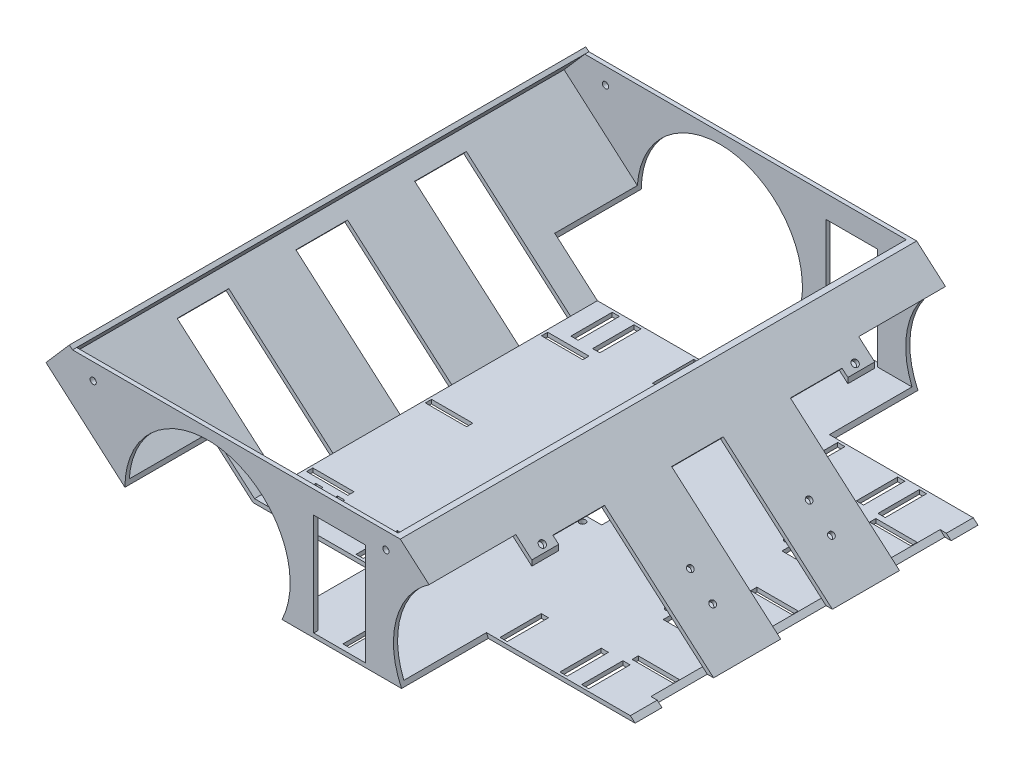
SolidWorks part; units mm, degrees
material "AISI 304"
ref_plane "前视基准面" through (0, 0, 0) normal (0, 0, 1) x (1, 0, 0)
ref_plane "上视基准面" through (0, 0, 0) normal (0, 1, 0) x (1, 0, 0)
ref_plane "右视基准面" through (0, 0, 0) normal (1, 0, 0) x (0, 0, -1)
sketch "草图1" plane through (0, 0, 0) normal (0, 0, 1) x (1, 0, 0)
  line L0 (0, 0) -> (-185, 0)
  line L1 (-185, 0) -> (-256.6974, 62.3256)
  line L2 (-256.6974, 62.3256) -> (-71.6974, 62.3256)
  line L3 (-71.6974, 62.3256) -> (0, 0)
extrude "凸台-拉伸1" add sketch "草图1" along normal blind 250
shell "抽壳1" thickness 2 removed face at (-164.1974, 62.3256, 125)
sketch "草图4" plane through (0, 0, 250) normal (0, 0, 1) x (1, 0, 0)
  circle A0 centre (-35, 17.3) radius 40
  circle A1 centre (-165, 17.3) radius 40
extrude "切除-拉伸3" cut sketch "草图4" against normal blind 42
sketch "草图6" plane through (0, 0, 0) normal (0, 0, -1) x (-1, 0, 0)
  arc A0 (15.1851, -17.4472) -> (15.1851, 52.0472) centre (35, 17.3) ccw
  arc A1 (15.1851, 52.0472) -> (15.1851, -17.4472) centre (-5, 17.3) ccw
  circle A2 centre (165, 17.3) radius 40
extrude "切除-拉伸5" cut sketch "草图6" against normal blind 42 contours A2 | A0 A1
sketch "草图7" plane through (0, 2, 0) normal (0, 1, 0) x (1, 0, 0)
  line L0 (-184.2522, -125) -> (127.4873, -125) construction
  line L1 (-184.2522, -208) -> (-184.2522, -42) construction
  line L2 (-175.84, -206.75) -> (-172.34, -206.75)
  line L7 (-175.84, -206.75) -> (-175.84, -186.75)
  line L8 (-175.84, -186.75) -> (-172.34, -186.75)
  line L9 (-172.34, -206.75) -> (-172.34, -186.75)
  line L10 (-27.16, -206.75) -> (-23.66, -206.75)
  line L11 (-27.16, -206.75) -> (-27.16, -186.75)
  line L12 (-27.16, -186.75) -> (-23.66, -186.75)
  line L13 (-23.66, -206.75) -> (-23.66, -186.75)
  line L14 (-165.34, -206.75) -> (-161.84, -206.75)
  line L15 (-165.34, -206.75) -> (-165.34, -186.75)
  line L16 (-165.34, -186.75) -> (-161.84, -186.75)
  line L17 (-161.84, -206.75) -> (-161.84, -186.75)
  line L18 (-136.34, -206.75) -> (-132.84, -206.75)
  line L19 (-136.34, -206.75) -> (-136.34, -186.75)
  line L20 (-136.34, -186.75) -> (-132.84, -186.75)
  line L21 (-132.84, -206.75) -> (-132.84, -186.75)
  line L22 (-34.16, -206.75) -> (-37.66, -206.75)
  line L23 (-34.16, -206.75) -> (-34.16, -186.75)
  line L24 (-34.16, -186.75) -> (-37.66, -186.75)
  line L25 (-37.66, -206.75) -> (-37.66, -186.75)
  line L26 (-63.16, -206.75) -> (-66.66, -206.75)
  line L27 (-63.16, -206.75) -> (-63.16, -186.75)
  line L28 (-63.16, -186.75) -> (-66.66, -186.75)
  line L29 (-66.66, -206.75) -> (-66.66, -186.75)
  line L30 (-132.84, -43.25) -> (-132.84, -63.25)
  line L31 (-136.34, -63.25) -> (-132.84, -63.25)
  line L32 (-136.34, -43.25) -> (-136.34, -63.25)
  line L33 (-136.34, -43.25) -> (-132.84, -43.25)
  line L34 (-161.84, -43.25) -> (-161.84, -63.25)
  line L35 (-165.34, -63.25) -> (-161.84, -63.25)
  line L36 (-165.34, -43.25) -> (-165.34, -63.25)
  line L37 (-165.34, -43.25) -> (-161.84, -43.25)
  line L38 (-172.34, -43.25) -> (-172.34, -63.25)
  line L39 (-175.84, -63.25) -> (-172.34, -63.25)
  line L40 (-175.84, -43.25) -> (-175.84, -63.25)
  line L41 (-175.84, -43.25) -> (-172.34, -43.25)
  line L42 (-66.66, -43.25) -> (-66.66, -63.25)
  line L43 (-63.16, -63.25) -> (-66.66, -63.25)
  line L44 (-63.16, -43.25) -> (-63.16, -63.25)
  line L45 (-63.16, -43.25) -> (-66.66, -43.25)
  line L46 (-37.66, -43.25) -> (-37.66, -63.25)
  line L47 (-34.16, -63.25) -> (-37.66, -63.25)
  line L48 (-34.16, -43.25) -> (-34.16, -63.25)
  line L49 (-34.16, -43.25) -> (-37.66, -43.25)
  line L50 (-23.66, -43.25) -> (-23.66, -63.25)
  line L51 (-27.16, -63.25) -> (-23.66, -63.25)
  line L52 (-27.16, -43.25) -> (-27.16, -63.25)
  line L53 (-27.16, -43.25) -> (-23.66, -43.25)
  line L54 (-24.66, -90.25) -> (-24.66, -105.5276) construction
  line L55 (-101.1743, -135) -> (-89.1743, -135)
  line L56 (-101.1743, -135) -> (-101.1743, -115)
  line L57 (-101.1743, -115) -> (-89.1743, -115)
  line L58 (-89.1743, -135) -> (-89.1743, -115)
  line L59 (-101.1743, -135) -> (-89.1743, -115) construction
  line L60 (-101.1743, -115) -> (-89.1743, -135) construction
  line L61 (-34.66, -90.25) -> (-14.66, -90.25)
  line L62 (-34.66, -90.25) -> (-34.66, -102.25)
  line L63 (-34.66, -102.25) -> (-14.66, -102.25)
  line L64 (-14.66, -90.25) -> (-14.66, -102.25)
  line L65 (-14.66, -159.75) -> (-14.66, -147.75)
  line L66 (-34.66, -147.75) -> (-14.66, -147.75)
  line L67 (-34.66, -159.75) -> (-34.66, -147.75)
  line L68 (-34.66, -159.75) -> (-14.66, -159.75)
  circle A0 centre (-95.1743, -111.75) radius 1.5
  circle A1 centre (-95.1743, -138.25) radius 1.5
  circle A2 centre (-11.41, -96.25) radius 1.5
  circle A3 centre (-37.91, -96.25) radius 1.5
  circle A4 centre (-37.91, -153.75) radius 1.5
  circle A5 centre (-11.41, -153.75) radius 1.5
  point P52 (-95.1743, -125)
  dimension "D2" = 29
  dimension "D3" = 26.5
  dimension "D6" = 3
  dimension "D1" = 10.5
  dimension "D4" = 26.5
  dimension "D5" = 20
  dimension "D7" = 81.75
  dimension "D8" = 81.75
  dimension "D9" = 81.75
  dimension "D10" = 81.75
extrude "切除-拉伸6" cut sketch "草图7" against normal blind 32
sketch "草图8" plane through (0, 0, 208) normal (0, 0, 1) x (1, 0, 0)
  line L1 (-50, 52) -> (0, 52)
  line L2 (-50, 52) -> (-50, 2)
  line L3 (-50, 2) -> (0, 2)
  line L4 (0, 52) -> (0, 2)
extrude "切除-拉伸7" cut sketch "草图8" against normal blind 15
sketch "草图9" plane through (0, 0, 42) normal (0, 0, -1) x (-1, 0, 0)
  line L0 (50, 2) -> (0, 2)
  line L2 (0, 2) -> (0, 50)
  line L3 (0, 50) -> (50, 50)
  line L4 (50, 2) -> (50, 50)
  line L5 (5.3492, 2) -> (71.9582, 2) construction
extrude "切除-拉伸8" cut sketch "草图9" against normal blind 15
sketch "草图10" plane through (0, 0, 0) normal (0.6561, 0.7547, 0) x (0.7547, -0.6561, 0)
  line L0 (0, -208) -> (0, -42) construction
  line L1 (0, -170) -> (-70, -170)
  line L2 (0, -170) -> (0, -195)
  line L3 (0, -195) -> (-70, -195)
  line L4 (-70, -170) -> (-70, -195)
  line L6 (0, -55) -> (-70, -55)
  line L7 (0, -55) -> (0, -80)
  line L8 (0, -80) -> (-70, -80)
  line L9 (-70, -55) -> (-70, -80)
  line L10 (0, -112.5) -> (-70, -112.5)
  line L11 (0, -112.5) -> (0, -137.5)
  line L12 (0, -137.5) -> (-70, -137.5)
  line L13 (-70, -112.5) -> (-70, -137.5)
extrude "切除-拉伸9" cut sketch "草图10" against normal blind 2
sketch "草图13" plane through (0, 0, 0) normal (0, 0, -1) x (-1, 0, 0)
  line L1 (88.6038, 51.4288) -> (113.6038, 51.4288)
  line L2 (88.6038, 51.4288) -> (88.6038, 2)
  line L4 (113.6038, 51.4288) -> (113.6038, 2)
  line L5 (88.6038, 2) -> (113.6038, 2)
extrude "切除-拉伸10" cut sketch "草图13" against normal blind 304
sketch "草图14" plane through (-78.3144, -90.0904, 0) normal (0.6561, 0.7547, 0) x (0.7547, -0.6561, 0)
  line L0 (-140.369, -208) -> (-140.369, -42) construction
  line L1 (-140.369, -55) -> (-207.2252, -55)
  line L2 (-140.369, -55) -> (-140.369, -80)
  line L3 (-140.369, -80) -> (-207.2252, -80)
  line L4 (-207.2252, -55) -> (-207.2252, -80)
  line L6 (-140.369, -112.5) -> (-207.2252, -112.5)
  line L7 (-140.369, -112.5) -> (-140.369, -137.5)
  line L8 (-140.369, -137.5) -> (-207.2252, -137.5)
  line L9 (-207.2252, -112.5) -> (-207.2252, -137.5)
  line L10 (-140.369, -170) -> (-207.2252, -170)
  line L11 (-140.369, -170) -> (-140.369, -195)
  line L12 (-140.369, -195) -> (-207.2252, -195)
  line L13 (-207.2252, -170) -> (-207.2252, -195)
extrude "切除-拉伸11" cut sketch "草图14" against normal blind 2
sketch "草图15" plane through (0, 0, 0) normal (0, -1, 0) x (1, 0, 0)
  line L5 (-185.5643, 195) -> (-160.5643, 195) construction
  line L6 (-185.5643, 195) -> (-185.5643, 170) construction
  line L7 (-185.5643, 170) -> (-160.5643, 170) construction
  line L8 (-160.5643, 195) -> (-160.5643, 170) construction
  line L13 (-128.9346, 250) -> (-71.0654, 250) construction
  line L14 (-185.5643, 80) -> (-160.5643, 80) construction
  line L15 (-185.5643, 80) -> (-185.5643, 57.495) construction
  line L16 (-185.5643, 57.495) -> (-160.5643, 57.495) construction
  line L17 (-160.5643, 80) -> (-160.5643, 57.495) construction
  line L18 (-3.0485, 195) -> (-27.8654, 195) construction
  line L19 (-3.0485, 195) -> (-3.0485, 170) construction
  line L20 (-3.0485, 170) -> (-27.8654, 170) construction
  line L21 (-27.8654, 195) -> (-27.8654, 170) construction
  line L22 (-3.0485, 137.5) -> (-28.0485, 137.5) construction
  line L23 (-3.0485, 137.5) -> (-3.0485, 112.5) construction
  line L24 (-3.0485, 112.5) -> (-28.0485, 112.5) construction
  line L25 (-28.0485, 137.5) -> (-28.0485, 112.5) construction
  line L26 (-3.0485, 80) -> (-28.0485, 80) construction
  line L27 (-3.0485, 80) -> (-3.0485, 54.8155) construction
  line L28 (-3.0485, 54.8155) -> (-28.0485, 54.8155) construction
  line L29 (-28.0485, 80) -> (-28.0485, 54.8155) construction
  line L30 (-185.5643, 137.5) -> (-160.5643, 137.5) construction
  line L31 (-185.5643, 137.5) -> (-185.5643, 112.5) construction
  line L32 (-185.5643, 112.5) -> (-160.5643, 112.5) construction
  line L33 (-160.5643, 137.5) -> (-160.5643, 112.5) construction
  line L34 (-113.9749, 250) -> (-86.951, 250) construction
  line L35 (-113.9749, 250) -> (-113.9749, 225) construction
  line L36 (-113.9749, 225) -> (-86.951, 225) construction
  line L37 (-86.951, 250) -> (-86.951, 225) construction
  line L38 (-128.9346, 0) -> (-71.0654, 0) construction
  line L39 (-113.2875, 0) -> (-88.2875, 0) construction
  line L40 (-113.2875, 0) -> (-113.2875, 25) construction
  line L41 (-113.2875, 25) -> (-88.2875, 25) construction
  line L42 (-88.2875, 0) -> (-88.2875, 25) construction
  line L43 (-86.951, 237.5) -> (-113.9749, 237.5) construction
  line L44 (-15.4569, 195) -> (-15.4569, 170) construction
  line L45 (-15.5485, 137.5) -> (-15.5485, 112.5) construction
  line L46 (-15.5485, 80) -> (-15.5485, 54.8155) construction
  line L47 (-88.2875, 12.5) -> (-113.2875, 12.5) construction
  line L48 (-173.0643, 195) -> (-173.0643, 170) construction
  line L49 (-173.0643, 137.5) -> (-173.0643, 112.5) construction
  line L50 (-173.0643, 80) -> (-173.0643, 57.495) construction
  line L52 (-98.963, 247.5) -> (-101.963, 247.5)
  line L53 (-98.963, 247.5) -> (-98.963, 227.5)
  line L54 (-98.963, 227.5) -> (-101.963, 227.5)
  line L55 (-101.963, 247.5) -> (-101.963, 227.5)
  line L56 (-98.963, 247.5) -> (-101.963, 227.5) construction
  line L57 (-98.963, 227.5) -> (-101.963, 247.5) construction
  line L58 (-5.4569, 184) -> (-25.4569, 184)
  line L59 (-5.4569, 184) -> (-5.4569, 181)
  line L60 (-5.4569, 181) -> (-25.4569, 181)
  line L61 (-25.4569, 184) -> (-25.4569, 181)
  line L62 (-5.4569, 184) -> (-25.4569, 181) construction
  line L63 (-5.4569, 181) -> (-25.4569, 184) construction
  line L64 (-5.5485, 126.5) -> (-25.5485, 126.5)
  line L65 (-5.5485, 126.5) -> (-5.5485, 123.5)
  line L66 (-5.5485, 123.5) -> (-25.5485, 123.5)
  line L67 (-25.5485, 126.5) -> (-25.5485, 123.5)
  line L68 (-5.5485, 126.5) -> (-25.5485, 123.5) construction
  line L69 (-5.5485, 123.5) -> (-25.5485, 126.5) construction
  line L70 (-5.5485, 68.9078) -> (-25.5485, 68.9078)
  line L71 (-5.5485, 68.9078) -> (-5.5485, 65.9078)
  line L72 (-5.5485, 65.9078) -> (-25.5485, 65.9078)
  line L73 (-25.5485, 68.9078) -> (-25.5485, 65.9078)
  line L74 (-5.5485, 68.9078) -> (-25.5485, 65.9078) construction
  line L75 (-5.5485, 65.9078) -> (-25.5485, 68.9078) construction
  line L76 (-99.2875, 22.5) -> (-102.2875, 22.5)
  line L77 (-99.2875, 22.5) -> (-99.2875, 2.5)
  line L78 (-99.2875, 2.5) -> (-102.2875, 2.5)
  line L79 (-102.2875, 22.5) -> (-102.2875, 2.5)
  line L80 (-99.2875, 22.5) -> (-102.2875, 2.5) construction
  line L81 (-99.2875, 2.5) -> (-102.2875, 22.5) construction
  line L82 (-163.0643, 70.2475) -> (-183.0643, 70.2475)
  line L83 (-163.0643, 70.2475) -> (-163.0643, 67.2475)
  line L84 (-163.0643, 67.2475) -> (-183.0643, 67.2475)
  line L85 (-183.0643, 70.2475) -> (-183.0643, 67.2475)
  line L86 (-163.0643, 70.2475) -> (-183.0643, 67.2475) construction
  line L87 (-163.0643, 67.2475) -> (-183.0643, 70.2475) construction
  line L88 (-163.0643, 126.5) -> (-183.0643, 126.5)
  line L89 (-163.0643, 126.5) -> (-163.0643, 123.5)
  line L90 (-163.0643, 123.5) -> (-183.0643, 123.5)
  line L91 (-183.0643, 126.5) -> (-183.0643, 123.5)
  line L92 (-163.0643, 126.5) -> (-183.0643, 123.5) construction
  line L93 (-163.0643, 123.5) -> (-183.0643, 126.5) construction
  line L94 (-163.0643, 184) -> (-183.0643, 184)
  line L95 (-163.0643, 184) -> (-163.0643, 181)
  line L96 (-163.0643, 181) -> (-183.0643, 181)
  line L97 (-183.0643, 184) -> (-183.0643, 181)
  line L98 (-163.0643, 184) -> (-183.0643, 181) construction
  line L99 (-163.0643, 181) -> (-183.0643, 184) construction
  point P58 (-100.463, 237.5)
  point P65 (-15.4569, 182.5)
  point P70 (-15.5485, 125)
  point P75 (-15.5485, 67.4078)
  point P80 (-100.7875, 12.5)
  point P85 (-173.0643, 68.7475)
  point P90 (-173.0643, 125)
  point P95 (-173.0643, 182.5)
extrude "切除-拉伸12" cut sketch "草图15" against normal blind 2
sketch "草图16" plane through (-1.3121, -1.5094, 0) normal (-0.6561, -0.7547, 0) x (0.7547, -0.6561, 0)
  circle A0 centre (-22.1612, 96.25) radius 1.5
  circle A1 centre (-36.4612, 96.25) radius 1.5
  circle A2 centre (-22.1612, 153.75) radius 1.5
  circle A3 centre (-36.4612, 153.75) radius 1.5
extrude "切除-拉伸13" cut sketch "草图16" against normal blind 90
sketch "草图18" plane through (0, 0, 0) normal (0.6561, 0.7547, 0) x (0.7547, -0.6561, 0)
  circle A0 centre (-69.1772, -200.7358) radius 1.6
  circle A1 centre (-69.1772, -49.2642) radius 1.6
extrude "切除-拉伸14" cut sketch "草图18" against normal blind 5
sketch "草图19" plane through (0, 0, 250) normal (0, 0, 1) x (1, 0, 0)
  line L0 (-256.6974, 62.3256) -> (-241.6974, 62.3256)
  line L1 (-71.6974, 62.3256) -> (-256.6974, 62.3256) construction
  line L3 (-256.6974, 62.3256) -> (-204.9999, 17.3857) construction
  line L5 (-256.6974, 62.3256) -> (-241.6974, 49.2863)
  line L6 (-241.6974, 49.2863) -> (-230.3625, 62.3256)
  line L7 (-230.3625, 62.3256) -> (-241.6974, 62.3256)
extrude "切除-拉伸15" cut sketch "草图19" against normal blind 264
sketch "草图20" plane through (-162.0709, 140.8861, 0) normal (-0.7547, 0.6561, 0) x (0, 0, 1)
  line L0 (0, -104.0937) -> (0, -121.3709) construction
  line L1 (0, -104.0937) -> (250, -104.0937)
  line L2 (0, -104.0937) -> (0, -121.3709)
  line L3 (0, -121.3709) -> (250, -121.3709)
  line L4 (250, -104.0937) -> (250, -121.3709)
extrude "凸台-拉伸2" add sketch "草图20" along normal blind 2
sketch "草图21" plane through (0, 0, 250) normal (0, 0, 1) x (1, 0, 0)
  line L0 (-88.6038, 51.4288) -> (-88.6038, 2) construction
  line L1 (-71.6974, 62.3256) -> (-230.3625, 62.3256) construction
  circle A0 centre (-78.6038, 54.3256) radius 1.5
  circle A1 centre (-220.3625, 54.3256) radius 1.5
  dimension "D1" = 3
  dimension "D4" = 3
  dimension "D2" = 10
  dimension "D3" = 8
  dimension "D5" = 10
extrude "切除-拉伸17" cut sketch "草图21" against normal through all both and the other way through all
